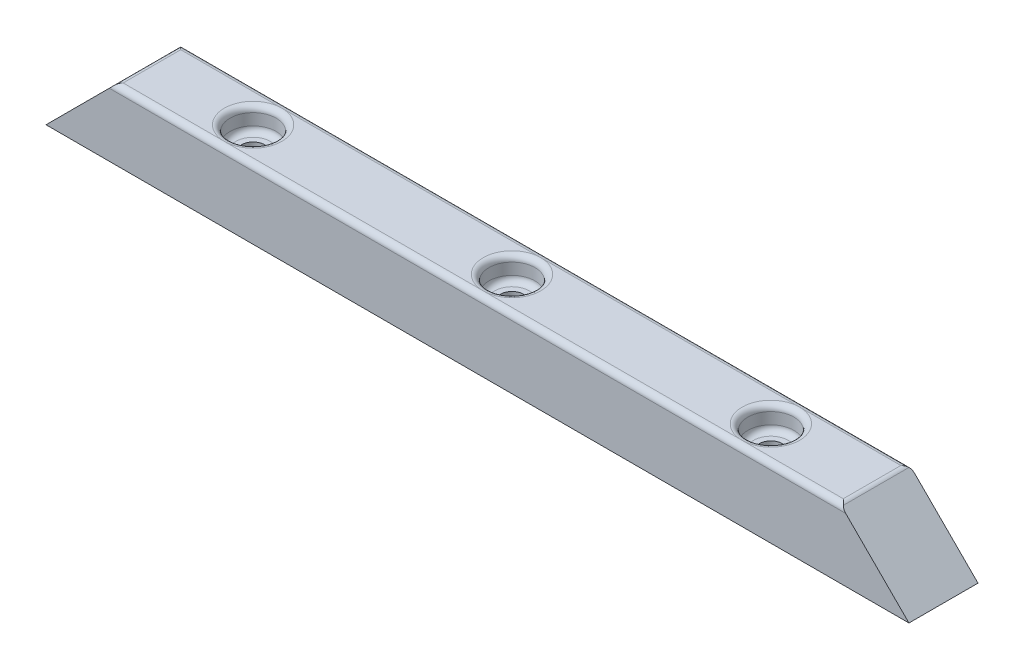
SolidWorks part; units mm, degrees
ref_plane "Front Plane" through (0, 0, 0) normal (0, 0, 1) x (1, 0, 0)
ref_plane "Top Plane" through (0, 0, 0) normal (0, 1, 0) x (1, 0, 0)
ref_plane "Right Plane" through (0, 0, 0) normal (1, 0, 0) x (0, 0, -1)
sketch "Sketch2" plane through (0, 0, 0) normal (0, 0, 1) x (1, 0, 0)
  line L0 (-75, -6) -> (-63, 6)
  line L1 (-75, -6) -> (75, -6)
  line L3 (-63, 6) -> (63, 6)
  line L5 (-75, -6) -> (63.8889, 5.1111) construction
  line L6 (-63.8889, 5.1111) -> (75, -6) construction
  line L7 (75, -6) -> (63, 6)
  point P0 (0, 0)
  dimension "D2" = 150
  dimension "D3" = 45
  dimension "D4" = 45
extrude "Boss-Extrude1" add sketch "Sketch2" along normal blind 12
sketch "Sketch3" plane through (0, 6, 0) normal (0, 1, 0) x (1, 0, 0)
  line L0 (63, -6) -> (-63, -6) construction
  line L1 (63, -12) -> (63, 0) construction
  line L2 (-63, -12) -> (-63, 0) construction
  circle A0 centre (0, -6) radius 2
  circle A1 centre (45, -6) radius 2
  circle A2 centre (-45, -6) radius 2
  dimension "D1" = 4
  dimension "D3" = 45
  dimension "D2" = 45
extrude "Cut-Extrude1" cut sketch "Sketch3" against normal blind 12
sketch "Sketch4" plane through (0, 6, 0) normal (0, 1, 0) x (1, 0, 0)
  circle A0 centre (-45, -6) radius 4
  circle A1 centre (0, -6) radius 4
  circle A2 centre (45, -6) radius 4
extrude "Cut-Extrude2" cut sketch "Sketch4" against normal blind 4
fillet "Fillet1" radius 1 3 edges at (-49, 6, 6) (41, 6, 6) (-4, 6, 6)
fillet "Fillet2" radius 1 3 edges at (-49, 2, 6) (-4, 2, 6) (41, 2, 6)
fillet "Fillet3" radius 1 4 edges at (-63, 6, 6) (63, 6, 6) (0, 6, 12) (0, 6, 0)
